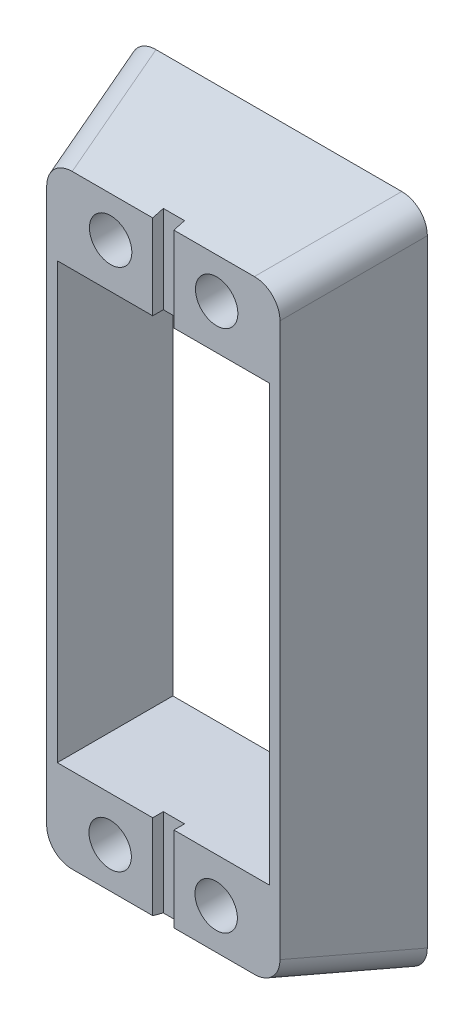
SolidWorks part; units mm, degrees
ref_plane "Front Plane" through (0, 0, 0) normal (0, 0, 1) x (1, 0, 0)
ref_plane "Top Plane" through (0, 0, 0) normal (0, 1, 0) x (1, 0, 0)
ref_plane "Right Plane" through (0, 0, 0) normal (1, 0, 0) x (0, 0, -1)
sketch "Sketch1" plane through (0, 0, 0) normal (0, 0, 1) x (1, 0, 0)
  line L0 (10, 9.75) -> (-10, 9.75) construction
  line L1 (10, -10.75) -> (10, 30.25) construction
  line L2 (-10, 30.25) -> (-10, -10.75) construction
  line L3 (0, 30.2379) -> (0, -10.75) construction
  line L4 (8.9, 30.2379) -> (-8.9, 30.2379) construction
  line L5 (-10, -10.75) -> (10, -10.75) construction
  line L6 (-3.75, 37.25) -> (3.75, 37.25) construction
  line L7 (-14, -21.75) -> (14, -21.75)
  line L8 (-14, -21.75) -> (-14, 41.25)
  line L9 (-14, 41.25) -> (14, 41.25)
  line L10 (14, -21.75) -> (14, 41.25)
  line L11 (-14, -21.75) -> (14, 41.25) construction
  line L12 (-14, 41.25) -> (14, -21.75) construction
  line L14 (-10, -10.75) -> (10, -10.75)
  line L15 (-10, -10.75) -> (-10, 30.25)
  line L16 (-10, 30.25) -> (10, 30.25)
  line L17 (10, -10.75) -> (10, 30.25)
  line L18 (-10, -10.75) -> (10, 30.25) construction
  line L19 (-10, 30.25) -> (10, -10.75) construction
  point P12 (0, 9.75)
  point P19 (0, 9.75)
  dimension "D1" = 4
  dimension "D2" = 4
extrude "Boss-Extrude1" add sketch "Sketch1" along normal blind 10.9
sketch "Sketch2" plane through (0, 0, 0) normal (0, 0, -1) x (-1, 0, 0)
  circle A0 centre (5.0132, -14.95) radius 2
  circle A1 centre (-4.9868, -14.95) radius 2
  circle A2 centre (-5.0305, 34.45) radius 2
  circle A3 centre (4.9695, 34.45) radius 2
extrude "Cut-Extrude1" cut sketch "Sketch2" against normal through all
chamfer "Chamfer1" distance 10.9 distance2 3 4 edges at (14, 9.75, 10.9) (0, -21.75, 10.9) (-14, 9.75, 10.9) (0, 41.25, 10.9) first distance on face at (14, 9.75, 5.45) first distance on face at (0, -21.75, 5.45) first distance on face at (-14, 9.75, 5.45) first distance on face at (0, 41.25, 5.45)
ref_plane "Plane1" through (0, 40, 0) normal (0, 1, 0) x (1, 0, 0)
sketch "Sketch3" plane through (0, 40, 0) normal (0, 1, 0) x (1, 0, 0)
  line L1 (-1, -10.9) -> (1, -10.9)
  line L2 (-1, -10.9) -> (-1, -9.9)
  line L3 (-1, -9.9) -> (1, -9.9)
  line L4 (1, -10.9) -> (1, -9.9)
  point P6 (0, -9.9)
  dimension "D1" = 2
  dimension "D2" = 1
extrude "Cut-Extrude2" cut sketch "Sketch3" against normal through all
fillet "Fillet1" radius 2.5 4 edges at (-12.5, -20.25, 5.45) (12.5, -20.25, 5.45) (-12.5, 39.75, 5.45) (12.5, 39.75, 5.45)
